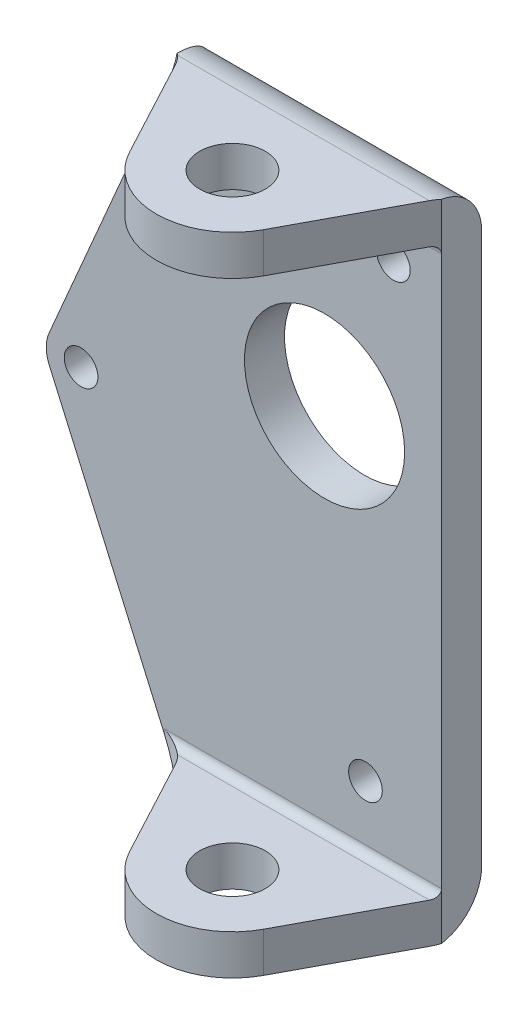
SolidWorks part; units mm, degrees
ref_plane "Front Plane" through (0, 0, 0) normal (0, 0, 1) x (1, 0, 0)
ref_plane "Top Plane" through (0, 0, 0) normal (0, 1, 0) x (1, 0, 0)
ref_plane "Right Plane" through (0, 0, 0) normal (1, 0, 0) x (0, 0, -1)
sketch "Sketch1" plane through (0, 0, 0) normal (1, 0, 0) x (0, 0, -1)
  line L0 (-15, 35.32) -> (10, 35.32)
  line L1 (-15, -40.32) -> (15, -40.32)
  line L2 (-15, -40.32) -> (-15, -35.32)
  line L3 (-15, 40.32) -> (15, 40.32)
  line L4 (15, -40.32) -> (15, 40.32)
  line L5 (-15, -40.32) -> (15, 40.32) construction
  line L6 (-15, 40.32) -> (15, -40.32) construction
  line L7 (10, 35.32) -> (10, -35.32)
  line L8 (10, -35.32) -> (-15, -35.32)
  line L9 (-15, 35.32) -> (-15, 40.32)
  point P0 (0, 0)
  dimension "D1" = 30
  dimension "D2" = 70.64
  dimension "D3" = 5
  dimension "D4" = 5
  dimension "D5" = 5
extrude "Boss-Extrude1" add sketch "Sketch1" along normal mid plane 49.52
sketch "Sketch2" plane through (0, 40.32, 0) normal (0, 1, 0) x (1, 0, 0)
  line L0 (24.76, 15) -> (-24.76, 15) construction
  line L1 (-24.76, -15) -> (-7.47, -15)
  line L2 (-24.76, -15) -> (-24.76, 10)
  line L3 (-24.76, 10) -> (-7.47, 10)
  line L4 (-7.47, -15) -> (-7.47, 10)
  dimension "D1" = 5
  dimension "D2" = 17.29
extrude "Cut-Extrude1" cut sketch "Sketch2" against normal through all
sketch "Sketch3" plane through (0, 40.32, 0) normal (0, 1, 0) x (1, 0, 0)
  line L0 (24.76, 0) -> (-7.47, 0) construction
  line L8 (24.76, 15) -> (24.76, -15) construction
  line L9 (-7.47, -15) -> (-7.47, 10) construction
  line L10 (8.645, -15) -> (8.645, 15) construction
  line L11 (24.76, -15) -> (-7.47, -15) construction
  line L12 (24.76, 15) -> (-24.76, 15) construction
  circle A4 centre (8.645, 0) radius 4.1
  dimension "D1" = 8.2
extrude "Cut-Extrude2" cut sketch "Sketch3" against normal through all contours A4 region at (8.645, 40.32, 0)
sketch "Sketch4" plane through (0, 0, -10) normal (0, 0, 1) x (1, 0, 0)
  line L0 (-24.76, 0) -> (24.76, 0) construction
  line L6 (-24.76, 40.32) -> (-24.76, -40.32) construction
  line L7 (24.76, 35.32) -> (24.76, -35.32) construction
  line L11 (-24.76, 40.32) -> (-24.76, -40.32) construction
  line L12 (24.76, -40.32) -> (-24.76, -40.32) construction
  circle A0 centre (15.25, -27.43) radius 2.1
  circle A1 centre (18.74, 30.57) radius 2.1
  circle A3 centre (-20.26, -0.44) radius 2.1
  dimension "D1" = 3.49
  dimension "D2" = 58
  dimension "D3" = 39
  dimension "D4" = 4.5
  dimension "D5" = 4.2
  dimension "D6" = 31.01
  dimension "D7" = 39.88
extrude "Cut-Extrude3" cut sketch "Sketch4" against normal through all
sketch "Sketch6" plane through (0, 0, -10) normal (0, 0, 1) x (1, 0, 0)
  line L0 (-7.47, 40.32) -> (-24.2508, 1.2752)
  line L1 (-7.47, -40.32) -> (-24.2363, -2.1884)
  line L2 (-7.47, 40.32) -> (-24.76, 40.32)
  line L3 (-24.76, 40.32) -> (-24.76, -40.32)
  line L4 (-24.76, -40.32) -> (-7.47, -40.32)
  arc A0 (-24.2508, 1.2752) -> (-24.2363, -2.1884) centre (-20.26, -0.44) ccw
  line M6 (-7.47, 40.32) -> (-24.76, 40.32)
  line M7 (-24.76, 40.32) -> (-24.76, -40.32)
  line M8 (-24.76, -40.32) -> (-7.47, -40.32)
extrude "Cut-Extrude4" cut sketch "Sketch6" against normal through all contours A0 L0 M6 M7 | A0 L1 M7 M8 region at (-16.6181, 21.1232, -10)
sketch "Sketch7" plane through (0, 40.32, 0) normal (0, 1, 0) x (1, 0, 0)
  line L0 (-7.47, 10) -> (0.2663, -4.4773)
  line L1 (24.76, 10) -> (17.0237, -4.4773)
  line L2 (-7.47, 10) -> (-7.47, -15)
  line L3 (-7.47, -15) -> (24.76, -15)
  line L4 (24.76, -15) -> (24.76, 10)
  arc A0 (0.2663, -4.4773) -> (17.0237, -4.4773) centre (8.645, 0) ccw
  dimension "D1" = 19
extrude "Cut-Extrude5" cut sketch "Sketch7" against normal through all
sketch "Sketch8" plane through (0, 0, -10) normal (0, 0, 1) x (1, 0, 0)
  circle A0 centre (10.14, 10.57) radius 10
  circle A3 centre (18.74, 30.57) radius 2.1 construction
  dimension "D1" = 20
  dimension "D2" = 20
  dimension "D3" = 8.6
extrude "Cut-Extrude6" cut sketch "Sketch8" against normal through all
fillet "Fillet1" radius 1 2 edges at (8.645, 35.32, -10) (8.645, -35.32, -10)
fillet "Fillet2" radius 6 2 edges at (8.645, 40.32, -15) (8.645, -40.32, -15)
fillet "Fillet3" radius 4 2 edges at (-7.47, 37.278, -10) (-7.47, -37.278, -10)
